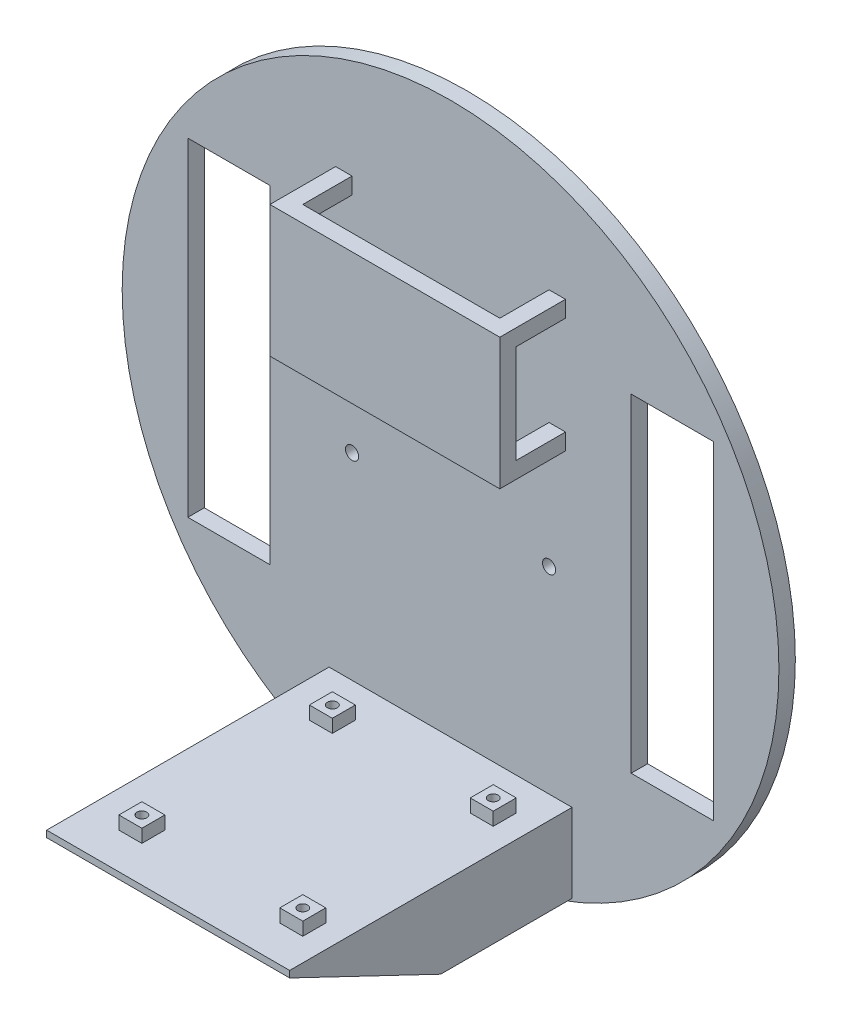
SolidWorks part; units mm, degrees
ref_plane "Płaszczyzna przednia" through (0, 0, 0) normal (0, 0, 1) x (1, 0, 0)
ref_plane "Płaszczyzna górna" through (0, 0, 0) normal (0, 1, 0) x (1, 0, 0)
ref_plane "Płaszczyzna prawa" through (0, 0, 0) normal (1, 0, 0) x (0, 0, -1)
sketch "Szkic1" plane through (0, 0, 0) normal (0, 0, 1) x (1, 0, 0)
  circle A0 centre (0, 0) radius 100
  dimension "D1" = 200
extrude "Dodanie-wyciągnięcie1" add sketch "Szkic1" along normal blind 5
sketch "Szkic2" plane through (0, 0, 5) normal (0, 0, 1) x (1, 0, 0)
  line L1 (-30, 10) -> (30, 10)
  line L2 (-30, 10) -> (-30, -60)
  line L3 (-30, -60) -> (30, -60)
  line L4 (30, 10) -> (30, -60)
  line L5 (-80, 50) -> (-55, 50)
  line L6 (-80, 50) -> (-80, -50)
  line L7 (-80, -50) -> (-55, -50)
  line L8 (-55, 50) -> (-55, -50)
  line L9 (55, 50) -> (80, 50)
  line L10 (55, 50) -> (55, -50)
  line L11 (55, -50) -> (80, -50)
  line L12 (80, 50) -> (80, -50)
  circle A0 centre (-30, -8) radius 2
  circle A1 centre (30, -8) radius 2
  dimension "D13" = 4
  dimension "D14" = 4
  dimension "D1" = 70
  dimension "D2" = 60
  dimension "D3" = 30
  dimension "D4" = 100
  dimension "D5" = 100
  dimension "D6" = 50
  dimension "D7" = 50
  dimension "D8" = 25
  dimension "D9" = 25
  dimension "D10" = 25
  dimension "D11" = 25
  dimension "D12" = 10
  dimension "D15" = 18
  dimension "D16" = 18
extrude "Wytnij-wyciągnięcie1" cut sketch "Szkic2" against normal blind 5 contours L8 L5 L6 L7 | L12 L9 L10 L11 | L2 A0 | L2 A0 | L4 A1 | L4 A1 region at (-29.1512, -8, 5) region at (-30.8488, -8, 5) region at (30.8488, -8, 5) region at (29.1512, -8, 5) region at (-67.5, 0, 5) region at (67.5, 0, 5)
sketch "Szkic3" plane through (0, 0, 5) normal (0, 0, 1) x (1, 0, 0)
  line L1 (-35, 65) -> (35, 65)
  line L2 (-35, 65) -> (-35, 25)
  line L3 (-35, 25) -> (35, 25)
  line L4 (35, 65) -> (35, 25)
  dimension "D1" = 70
  dimension "D2" = 40
  dimension "D3" = 35
  dimension "D4" = 25
extrude "Dodanie-wyciągnięcie2" add sketch "Szkic3" along normal blind 20
sketch "Szkic4" plane through (0, 0, 5) normal (0, 0, 1) x (1, 0, 0)
  line L0 (-30, -60) -> (30, -60) construction
  line L1 (-35, -70) -> (35, -70)
  line L2 (-35, -70) -> (-35, -90)
  line L3 (-35, -90) -> (35, -90)
  line L4 (35, -70) -> (35, -90)
  line L6 (-37, -68) -> (37, -68)
  line L7 (-37, -68) -> (-37, -92)
  line L8 (-37, -92) -> (37, -92)
  line L9 (37, -68) -> (37, -92)
  dimension "D1" = 20
  dimension "D2" = 70
  dimension "D3" = 10
  dimension "D4" = 35
  dimension "D5" = 24
  dimension "D6" = 74
  dimension "D7" = 2
  dimension "D8" = 2
extrude "Dodanie-wyciągnięcie3" add sketch "Szkic4" along normal blind 40
sketch "Szkic6" plane through (0, -68, 0) normal (0, 1, 0) x (1, 0, 0)
  line L1 (30, -80) -> (23, -80)
  line L2 (30, -80) -> (30, -73)
  line L3 (30, -73) -> (23, -73)
  line L4 (23, -80) -> (23, -73)
  line L5 (37, -5) -> (-37, -5) construction
  line L6 (-19, -80) -> (-26, -80)
  line L7 (-19, -80) -> (-19, -73)
  line L8 (-19, -73) -> (-26, -73)
  line L9 (-26, -80) -> (-26, -73)
  line L10 (30, -22) -> (23, -22)
  line L11 (30, -22) -> (30, -15)
  line L12 (30, -15) -> (23, -15)
  line L13 (23, -22) -> (23, -15)
  line L14 (-19, -22) -> (-26, -22)
  line L15 (-19, -22) -> (-19, -15)
  line L16 (-19, -15) -> (-26, -15)
  line L17 (-26, -22) -> (-26, -15)
  line L18 (30, -100) -> (-26, -100)
  line L19 (30, -100) -> (30, -15)
  line L20 (30, -15) -> (-26, -15)
  line L21 (-26, -100) -> (-26, -15)
  line L22 (37, -45) -> (37, -5) construction
  circle A0 centre (26.5, -18.5) radius 1.5
  circle A1 centre (-22.5, -18.5) radius 1.5
  circle A2 centre (26.5, -76.5) radius 1.5
  circle A3 centre (-22.5, -76.5) radius 1.5
  point P4 (23, -18.5)
  point P5 (26.5, -22)
  point P26 (2, -15)
  point P27 (-22.5, -22)
  point P28 (-19, -18.5)
  point P29 (30, -76.5)
  point P30 (-26, -76.5)
  point P31 (-22.5, -80)
  point P32 (26.5, -80)
  point P43 (26.3103, -73)
  point P44 (26.244, -73)
  dimension "D21" = 3
  dimension "D22" = 3
  dimension "D23" = 3
  dimension "D24" = 3
  dimension "D1" = 7
  dimension "D2" = 7
  dimension "D3" = 7
  dimension "D4" = 7
  dimension "D5" = 7
  dimension "D6" = 7
  dimension "D7" = 7
  dimension "D8" = 7
  dimension "D9" = 85
  dimension "D10" = 56
  dimension "D11" = 10
  dimension "D12" = 35
  dimension "D13" = 3.5
  dimension "D14" = 3.5
  dimension "D15" = 3.5
  dimension "D16" = 3.5
  dimension "D17" = 58
  dimension "D18" = 58
  dimension "D19" = 3.5
  dimension "D20" = 3.5
  dimension "D25" = 3.5
  dimension "D26" = 3.5
  dimension "D27" = 3.5
  dimension "D28" = 3.5
  dimension "D29" = 3.5
  dimension "D30" = 3.5
  dimension "D31" = 3.5
  dimension "D32" = 3.5
extrude "Dodanie-wyciągnięcie4" add sketch "Szkic6" along normal blind 4 contours L4 L1 L2 L3 A2 | L9 L6 L7 L8 A3 | L17 L14 L15 L16 A1 | L13 L10 L11 L12 A0 region at (26.5, -68, 79.901) region at (26.5, -68, 21.901) region at (-25.901, -68, 76.5) region at (-19.099, -68, 18.5)
sketch "Szkic7" plane through (0, 0, 45) normal (0, 0, 1) x (1, 0, 0)
  line L0 (37, -92) -> (37, -68) construction
  line L1 (-37, -68) -> (37, -68)
  line L2 (-37, -68) -> (-37, -70)
  line L3 (-37, -70) -> (37, -70)
  line L4 (37, -68) -> (37, -70)
  dimension "D1" = 2
extrude "Dodanie-wyciągnięcie5" add sketch "Szkic7" along normal blind 46
sketch "Szkic8" plane through (37, 0, 0) normal (1, 0, 0) x (0, 0, -1)
  line L0 (-91, -70) -> (-45, -92)
  line L1 (-45, -92) -> (-45, -70)
  line L2 (-45, -70) -> (-91, -70)
extrude "Dodanie-wyciągnięcie6" add sketch "Szkic8" against normal blind 2
extrude "Dodanie-wyciągnięcie7" add sketch "Szkic8<2>" along normal blind 2 from surface starting at face at (-37, -76.6667, 47)
sketch "Szkic8<2>" plane through (37, 0, 0) normal (1, 0, 0) x (0, 0, -1) same geometry as "Szkic8"
sketch "Szkic9" plane through (0, 65, 0) normal (0, 1, 0) x (1, 0, 0)
  line L0 (35, -5) -> (-35, -5) construction
  line L1 (30, -5) -> (-30, -5)
  line L2 (30, -5) -> (30, -20)
  line L3 (30, -20) -> (-30, -20)
  line L4 (-30, -5) -> (-30, -20)
  line L5 (35, -25) -> (35, -5) construction
  dimension "D1" = 60
  dimension "D2" = 15
  dimension "D3" = 5
sketch "Szkic10" plane through (35, 0, 0) normal (1, 0, 0) x (0, 0, -1)
  line L0 (-5, 25) -> (-5, 65) construction
  line L1 (-5, 30) -> (-20, 30)
  line L2 (-5, 30) -> (-5, 60)
  line L3 (-5, 60) -> (-20, 60)
  line L4 (-20, 30) -> (-20, 60)
  line L6 (-25, 25) -> (-5, 25) construction
  dimension "D1" = 30
  dimension "D2" = 5
  dimension "D3" = 15
extrude "Wytnij-wyciągnięcie2" cut sketch "Szkic9" against normal blind 40
extrude "Wytnij-wyciągnięcie3" cut sketch "Szkic10" against normal blind 70
